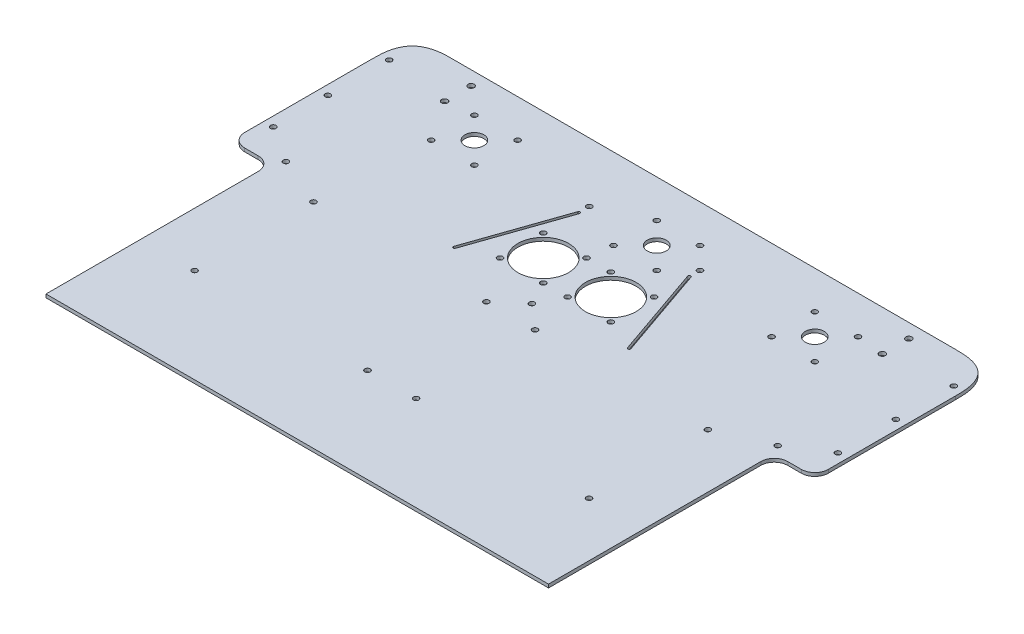
SolidWorks part; units mm, degrees
ref_plane "Front Plane" through (0, 0, 0) normal (0, 0, 1) x (1, 0, 0)
ref_plane "Top Plane" through (0, 0, 0) normal (0, 1, 0) x (1, 0, 0)
ref_plane "Right Plane" through (0, 0, 0) normal (1, 0, 0) x (0, 0, -1)
sketch "Sketch1" plane through (0, 0, 0) normal (0, 1, 0) x (1, 0, 0)
  line L1 (-103.134, 171.9149) -> (328.866, 171.9149)
  line L2 (-103.134, 171.9149) -> (-103.134, -28.0851)
  line L3 (-103.134, -28.0851) -> (328.866, -28.0851)
  line L4 (328.866, 171.9149) -> (328.866, -28.0851)
extrude "Boss-Extrude1" add sketch "Sketch1" along normal blind 2.5 contours L1 L4 L3 L2
sketch "Sketch3" plane through (0, 2.5, 0) normal (0, 1, 0) x (1, 0, 0)
  line L0 (-13.134, 71.9149) -> (-29.1359, 55.9131)
  line L1 (2.8678, 87.9167) -> (-29.1359, 87.9167)
  line L2 (2.8678, 87.9167) -> (2.8678, 55.9131)
  line L3 (2.8678, 55.9131) -> (-29.1359, 55.9131)
  line L4 (-29.1359, 87.9167) -> (-29.1359, 55.9131)
  line L5 (2.8678, 87.9167) -> (-29.1359, 55.9131) construction
  line L6 (2.8678, 55.9131) -> (-29.1359, 87.9167) construction
  line L7 (-103.134, 71.9149) -> (-13.134, 71.9149)
  line L8 (-103.134, 171.9149) -> (-103.134, -28.0851) construction
  line L9 (238.866, 71.9149) -> (238.866, 115.9149)
  line L14 (62.253, -0.3819) -> (46.2512, -16.3837)
  line L15 (238.866, 115.9149) -> (328.866, 115.9149)
  line L18 (328.866, 171.9149) -> (328.866, -28.0851) construction
  line L19 (238.866, 71.9149) -> (222.8641, 55.9131)
  line L20 (254.8678, 87.9167) -> (222.8641, 87.9167)
  line L21 (254.8678, 87.9167) -> (254.8678, 55.9131)
  line L22 (254.8678, 55.9131) -> (222.8641, 55.9131)
  line L23 (222.8641, 87.9167) -> (222.8641, 55.9131)
  line L24 (254.8678, 87.9167) -> (222.8641, 55.9131) construction
  line L25 (254.8678, 55.9131) -> (222.8641, 87.9167) construction
  line L27 (328.866, 71.9149) -> (238.866, 71.9149)
  line L28 (238.866, 115.9149) -> (238.866, 171.9149)
  line L29 (238.866, 171.9149) -> (328.866, 171.9149)
  line L30 (328.866, 115.9149) -> (328.866, 171.9149)
  line L31 (328.866, 115.9149) -> (-169.3435, 115.9149)
  line L32 (328.866, 115.9149) -> (328.866, 173.2785)
  line L33 (328.866, 173.2785) -> (-169.3435, 173.2785)
  line L34 (-169.3435, 115.9149) -> (-169.3435, 173.2785)
  line L35 (78.2549, 15.6199) -> (46.2512, 15.6199)
  line L36 (78.2549, 15.6199) -> (78.2549, -16.3837)
  line L37 (78.2549, -16.3837) -> (46.2512, -16.3837)
  line L38 (46.2512, 15.6199) -> (46.2512, -16.3837)
  line L39 (78.2549, 15.6199) -> (46.2512, -16.3837) construction
  line L40 (78.2549, -16.3837) -> (46.2512, 15.6199) construction
  circle A0 centre (-13.134, 71.9149) radius 7
  circle A1 centre (-29.1359, 55.9131) radius 2
  circle A2 centre (-29.1359, 87.9167) radius 2
  circle A3 centre (2.8678, 87.9167) radius 2
  circle A4 centre (2.8678, 55.9131) radius 2
  circle A10 centre (238.866, 71.9149) radius 7
  circle A11 centre (222.8641, 55.9131) radius 2
  circle A12 centre (222.8641, 87.9167) radius 2
  circle A13 centre (254.8678, 87.9167) radius 2
  circle A14 centre (254.8678, 55.9131) radius 2
  circle A15 centre (62.253, -0.3819) radius 7
  circle A16 centre (46.2512, -16.3837) radius 2
  circle A17 centre (46.2512, 15.6199) radius 2
  circle A18 centre (78.2549, 15.6199) radius 2
  circle A19 centre (78.2549, -16.3837) radius 2
  point P10 (328.866, 71.9149)
extrude "Cut-Extrude1" cut sketch "Sketch3" against normal blind 2.5 contours A2 | A3 | A4 | A1 | A0 | A11 | A14 | A13 | A10 | A12 | L32 L31 L34 L33
sketch "Sketch5" plane through (0, 2.5, 0) normal (0, 1, 0) x (1, 0, 0)
  line L0 (263.7413, -28.0851) -> (263.7413, -18.0851)
  line L3 (-103.134, -28.0851) -> (328.866, -28.0851) construction
  line L5 (263.7413, -18.0851) -> (328.866, -18.0851)
  line L6 (263.7413, -18.0851) -> (263.7413, -28.0851)
  line L7 (263.7413, -28.0851) -> (328.866, -28.0851)
  line L8 (328.866, -18.0851) -> (328.866, -28.0851)
  line L9 (263.7413, -18.0851) -> (-103.134, -18.0851)
  line L10 (263.7413, -18.0851) -> (263.7413, -28.0851)
  line L11 (263.7413, -28.0851) -> (-103.134, -28.0851)
  line L12 (-103.134, -18.0851) -> (-103.134, -28.0851)
  line M12 (328.866, -28.0851) -> (328.866, 115.9149)
  line M14 (-103.134, 115.9149) -> (-103.134, -28.0851)
  line M15 (-103.134, -28.0851) -> (328.866, -28.0851)
extrude "Cut-Extrude3" cut sketch "Sketch5" against normal blind 2.5 contours L0 L9 M14 M15 | L5 L0 M15 M12 region at (80.3036, 2.5, 23.0851) region at (296.3036, 2.5, 23.0851)
sketch "Sketch6" plane through (0, 2.5, 0) normal (0, 1, 0) x (1, 0, 0)
  line L0 (328.866, -18.0851) -> (-103.134, -18.0851) construction
  line L1 (112.866, -18.0851) -> (112.866, 21.9149)
  line L2 (112.866, 21.9149) -> (137.866, 21.9149)
  line L3 (112.866, 21.9149) -> (87.866, 21.9149)
  line L4 (87.866, 21.9149) -> (71.8641, 5.9131)
  line L5 (103.8678, 37.9167) -> (71.8641, 37.9167)
  line L6 (103.8678, 37.9167) -> (103.8678, 5.9131)
  line L7 (103.8678, 5.9131) -> (71.8641, 5.9131)
  line L8 (71.8641, 37.9167) -> (71.8641, 5.9131)
  line L9 (103.8678, 37.9167) -> (71.8641, 5.9131) construction
  line L10 (103.8678, 5.9131) -> (71.8641, 37.9167) construction
  line L11 (137.866, 21.9149) -> (121.8641, 5.9131)
  line L12 (153.8678, 37.9167) -> (121.8641, 37.9167)
  line L13 (153.8678, 37.9167) -> (153.8678, 5.9131)
  line L14 (153.8678, 5.9131) -> (121.8641, 5.9131)
  line L15 (121.8641, 37.9167) -> (121.8641, 5.9131)
  line L16 (153.8678, 37.9167) -> (121.8641, 5.9131) construction
  line L17 (153.8678, 5.9131) -> (121.8641, 37.9167) construction
  circle A0 centre (137.866, 21.9149) radius 18.75
  circle A1 centre (87.866, 21.9149) radius 18.75
  circle A2 centre (87.866, 21.9149) radius 7
  circle A3 centre (71.8641, 5.9131) radius 2
  circle A4 centre (71.8641, 37.9167) radius 2
  circle A5 centre (103.8678, 37.9167) radius 2
  circle A6 centre (103.8678, 5.9131) radius 2
  circle A7 centre (137.866, 21.9149) radius 7
  circle A8 centre (121.8641, 5.9131) radius 2
  circle A9 centre (121.8641, 37.9167) radius 2
  circle A10 centre (153.8678, 37.9167) radius 2
  circle A11 centre (153.8678, 5.9131) radius 2
  point P0 (112.866, -18.0851)
extrude "Cut-Extrude4" cut sketch "Sketch6" against normal blind 2.5 contours A11 | A8 | A10 | A9 | A5 | A6 | A3 | A4
sketch "Sketch8" plane through (0, 2.5, 0) normal (0, 1, 0) x (1, 0, 0)
  line L2 (153.8678, 5.9131) -> (153.8678, 90.0973)
  line L3 (153.8678, 90.0973) -> (71.8641, 90.0973)
  line L4 (71.8641, 90.0973) -> (71.8641, 5.9131)
  line L5 (153.8678, 64.0929) -> (71.8641, 64.0929)
  line L10 (177.527, -4.0851) -> (153.8678, 64.0929) construction
  line L14 (176.5823, -4.4129) -> (152.9231, 63.7651)
  line L15 (178.4718, -3.7572) -> (154.8125, 64.4208)
  line L16 (48.2049, -4.0851) -> (71.8641, 64.0929) construction
  line L17 (47.2602, -3.7572) -> (70.9194, 64.4208)
  line L18 (49.1496, -4.4129) -> (72.8089, 63.7651)
  arc A6 (176.5823, -4.4129) -> (178.4718, -3.7572) centre (177.527, -4.0851) ccw
  arc A7 (154.8125, 64.4208) -> (152.9231, 63.7651) centre (153.8678, 64.0929) ccw
  arc A8 (47.2602, -3.7572) -> (49.1496, -4.4129) centre (48.2049, -4.0851) ccw
  arc A9 (72.8089, 63.7651) -> (70.9194, 64.4208) centre (71.8641, 64.0929) ccw
  point P17 (177.527, 5.9131)
  point P18 (48.2049, 5.9131)
  point P19 (165.6974, 30.0039)
  point P22 (112.866, -4.0851)
  point P27 (60.0345, 30.0039)
extrude "Cut-Extrude5" cut sketch "Sketch8" against normal blind 2.5 contours L17 A9 L18 A8 | L15 A7 L14 A6
fillet "Fillet1" radius 30 2 edges at (-103.134, 1.25, -115.9149) (328.866, 1.25, -115.9149) curvature continuous yes
sketch "Sketch9" plane through (0, 2.5, 0) normal (0, 1, 0) x (1, 0, 0)
  line L0 (328.866, 62.6221) -> (321.866, 62.6221)
  line L1 (328.866, 85.9149) -> (328.866, -18.0851) construction
  line L2 (321.866, 109.7214) -> (321.866, -11.8915)
  line L3 (321.866, 6.0103) -> (321.866, -11.8915)
  line L4 (321.866, 109.7214) -> (321.866, 91.8196)
  line L5 (321.866, 91.8196) -> (321.866, 109.7214)
  line L6 (-103.134, 46.4673) -> (-96.134, 46.4673)
  line L7 (-103.134, 85.9149) -> (-103.134, -18.0851) construction
  line L8 (-96.134, 46.4673) -> (-96.134, 109.7214)
  line L9 (-96.134, 109.7214) -> (-96.134, -11.8916)
  line L10 (-96.134, -11.8916) -> (-96.134, 6.0103)
  line L11 (-96.134, 109.7214) -> (-96.134, 97.3154)
  line L12 (-96.134, 109.7214) -> (-96.134, 91.8196)
  circle A0 centre (321.866, 6.0103) radius 2
  circle A1 centre (321.866, 48.9149) radius 2
  circle A2 centre (321.866, 91.8196) radius 2
  circle A3 centre (-96.134, 46.4673) radius 2
  circle A4 centre (-96.134, 91.8196) radius 2
  circle A5 centre (-96.134, 6.0103) radius 2
  spline S0 degree 2 poles (328.866, 85.9149) (328.866, 87.9765) (328.8467, 89.0459) (328.8162, 90.7467) (328.7231, 92.1742) (328.5043, 95.5283) (327.8783, 98.3317) (326.3274, 105.2776) (322.2688, 109.3319) (318.2198, 113.3765) (311.2895, 114.9258) (308.4764, 115.5546) (305.1048, 115.7733) (303.6844, 115.8655) (301.9893, 115.8958) (300.9233, 115.9149) (298.866, 115.9149) knots 0 0 0 0.0625 0.0625 0.125 0.125 0.25 0.25 0.5 0.5 0.75 0.75 0.875 0.875 0.9375 0.9375 1 1 1 construction
  spline S1 degree 2 poles (298.866, -18.0851) (300.9275, -18.0851) (301.997, -18.0659) (303.6978, -18.0353) (305.1253, -17.9422) (308.4794, -17.7234) (311.2827, -17.0975) (318.2287, -15.5466) (322.283, -11.4879) (326.3276, -7.4389) (327.8768, -0.5086) (328.5057, 2.3045) (328.7244, 5.6761) (328.8165, 7.0965) (328.8469, 8.7916) (328.866, 9.8575) (328.866, 11.9149) knots 0 0 0 0.0625 0.0625 0.125 0.125 0.25 0.25 0.5 0.5 0.75 0.75 0.875 0.875 0.9375 0.9375 1 1 1 construction
  spline S2 degree 2 poles (-73.134, 115.9149) (-75.1956, 115.9149) (-76.2651, 115.8957) (-77.9658, 115.8651) (-79.3933, 115.772) (-82.7474, 115.5532) (-85.5508, 114.9273) (-92.4967, 113.3764) (-96.551, 109.3177) (-100.5957, 105.2687) (-102.1449, 98.3384) (-102.7737, 95.5254) (-102.9924, 92.1538) (-103.0846, 90.7333) (-103.1149, 89.0383) (-103.134, 87.9723) (-103.134, 85.9149) knots 0 0 0 0.0625 0.0625 0.125 0.125 0.25 0.25 0.5 0.5 0.75 0.75 0.875 0.875 0.9375 0.9375 1 1 1 construction
  spline S3 degree 2 poles (-103.134, 11.9149) (-103.134, 9.8534) (-103.1148, 8.7839) (-103.0842, 7.0831) (-102.9911, 5.6556) (-102.7723, 2.3015) (-102.1464, -0.5019) (-100.5955, -7.4478) (-96.5368, -11.5021) (-92.4879, -15.5467) (-85.5575, -17.0959) (-82.7445, -17.7248) (-79.3729, -17.9435) (-77.9525, -18.0356) (-76.2574, -18.066) (-75.1914, -18.0851) (-73.134, -18.0851) knots 0 0 0 0.0625 0.0625 0.125 0.125 0.25 0.25 0.5 0.5 0.75 0.75 0.875 0.875 0.9375 0.9375 1 1 1 construction
extrude "Cut-Extrude6" cut sketch "Sketch9" against normal blind 2.5 contours A0 | A1 | A2 | A5 | A3 | A4
sketch "Sketch10" plane through (0, 2.5, 0) normal (0, 1, 0) x (1, 0, 0)
  line L0 (232.1904, -18.0851) -> (232.1904, -11.5851)
  line L1 (328.866, -18.0851) -> (-103.134, -18.0851) construction
  line L2 (322.1851, -11.5851) -> (-96.4532, -11.5851)
  line L3 (322.1851, -11.5851) -> (232.1904, -11.5851)
  line L4 (322.1851, -11.5851) -> (232.1904, -11.5851)
  line L5 (322.1851, -11.5851) -> (232.1904, -11.5851)
  line L6 (322.1851, -11.5851) -> (294.9418, -11.5851)
  line L7 (-96.4532, -11.5851) -> (-78.7572, -11.5851)
  line L8 (-96.4532, -11.5851) -> (-69.2097, -11.5851)
  circle A0 centre (112.866, -11.5851) radius 2
  circle A3 centre (294.9418, -11.5851) radius 2
  circle A4 centre (-69.2097, -11.5851) radius 2
  spline S0 degree 2 poles (298.866, -18.0851) (300.9275, -18.0851) (301.997, -18.0659) (303.6978, -18.0353) (305.1253, -17.9422) (308.4794, -17.7234) (311.2827, -17.0975) (318.2287, -15.5466) (322.283, -11.4879) (326.3276, -7.4389) (327.8768, -0.5086) (328.5057, 2.3045) (328.7244, 5.6761) (328.8165, 7.0965) (328.8469, 8.7916) (328.866, 9.8575) (328.866, 11.9149) knots 0 0 0 0.0625 0.0625 0.125 0.125 0.25 0.25 0.5 0.5 0.75 0.75 0.875 0.875 0.9375 0.9375 1 1 1 construction
  spline S1 degree 2 poles (-103.134, 11.9149) (-103.134, 9.8534) (-103.1148, 8.7839) (-103.0842, 7.0831) (-102.9911, 5.6556) (-102.7723, 2.3015) (-102.1464, -0.5019) (-100.5955, -7.4478) (-96.5368, -11.5021) (-92.4879, -15.5467) (-85.5575, -17.0959) (-82.7445, -17.7248) (-79.3729, -17.9435) (-77.9525, -18.0356) (-76.2574, -18.066) (-75.1914, -18.0851) (-73.134, -18.0851) knots 0 0 0 0.0625 0.0625 0.125 0.125 0.25 0.25 0.5 0.5 0.75 0.75 0.875 0.875 0.9375 0.9375 1 1 1 construction
extrude "Cut-Extrude7" cut sketch "Sketch10" against normal blind 2.5 contours A4 | A0 | A3
extrude "Cut-Extrude8" cut sketch "Sketch6<3>" against normal blind 10 contours A1 | A0
sketch "Sketch6<3>" plane through (0, 2.5, 0) normal (0, 1, 0) x (1, 0, 0) same geometry as "Sketch6"
sketch "Sketch12" plane through (0, 2.5, 0) normal (0, 1, 0) x (1, 0, 0)
  line L0 (121.8641, 37.9167) -> (121.8641, 71.9149)
  line L1 (238.866, 71.9149) -> (-13.134, 71.9149)
  line L3 (121.8641, 71.9149) -> (105.8623, 55.9131)
  line L4 (137.866, 87.9167) -> (105.8623, 87.9167)
  line L5 (137.866, 87.9167) -> (137.866, 55.9131)
  line L6 (137.866, 55.9131) -> (105.8623, 55.9131)
  line L7 (105.8623, 87.9167) -> (105.8623, 55.9131)
  line L8 (137.866, 87.9167) -> (105.8623, 55.9131) construction
  line L9 (137.866, 55.9131) -> (105.8623, 87.9167) construction
  circle A1 centre (121.8641, 71.9149) radius 7
  circle A2 centre (105.8623, 55.9131) radius 2
  circle A3 centre (105.8623, 87.9167) radius 2
  circle A4 centre (137.866, 87.9167) radius 2
  circle A5 centre (137.866, 55.9131) radius 2
extrude "Cut-Extrude9" cut sketch "Sketch12" against normal blind 10 contours A5 | A4 | A3 | A2 | A1
sketch "Sketch13" plane through (0, 2.5, 0) normal (0, 1, 0) x (1, 0, 0)
  line L0 (328.866, 85.9149) -> (274.866, 85.9149)
  line L1 (274.866, 85.9149) -> (274.866, 105.5149)
  line L2 (-103.134, 85.9149) -> (-49.134, 85.9149)
  line L3 (-49.134, 85.9149) -> (-49.134, 105.5149)
  circle A0 centre (274.866, 85.9149) radius 2.25
  circle A1 centre (274.866, 105.5149) radius 2.25
  circle A2 centre (-49.134, 85.9149) radius 2.25
  circle A3 centre (-49.134, 105.5149) radius 2.25
extrude "Cut-Extrude10" cut sketch "Sketch13" against normal blind 10 contours A0 | A1 | A2 | A3
sketch "Sketch14" plane through (0, 2.5, 0) normal (0, 1, 0) x (1, 0, 0)
  line L0 (153.8678, 37.9167) -> (121.8641, 71.9149)
  line L1 (121.8641, 71.9149) -> (153.8678, 71.9149)
  line L2 (71.8641, 37.9167) -> (71.8641, 71.9149)
  circle A0 centre (153.8678, 71.9149) radius 2
  circle A1 centre (71.8641, 71.9149) radius 2
extrude "Cut-Extrude12" cut sketch "Sketch14" against normal blind 2.5 contours A0 | A1
sketch "Sketch19" plane through (0, 2.5, 0) normal (0, 1, 0) x (1, 0, 0)
  line L0 (-73.134, -18.0851) -> (298.866, -18.0851)
  line L1 (-73.134, -18.0851) -> (-73.134, -185.2034)
  line L2 (298.866, -18.0851) -> (298.866, -185.2034)
  line L3 (-73.134, -185.2034) -> (298.866, -185.2034)
extrude "Boss-Extrude5" add sketch "Sketch19" against normal blind 2.5
fillet "Fillet3" radius 10 4 edges at (-103.134, 1.25, 18.0851) (-73.134, 1.25, 18.0851) (328.866, 1.25, 18.0851) (298.866, 1.25, 18.0851)
sketch "Sketch21" plane through (0, 2.5, 0) normal (0, 1, 0) x (1, 0, 0)
  line L1 (298.866, -185.2034) -> (258.866, -185.2034)
  line L2 (298.866, -185.2034) -> (298.866, -115.2034)
  line L3 (298.866, -115.2034) -> (258.866, -115.2034)
  line L4 (258.866, -185.2034) -> (258.866, -115.2034)
  line L5 (258.866, -115.2034) -> (130.866, -115.2034)
  line L6 (258.866, -115.2034) -> (258.866, -27.2034)
  line L7 (258.866, -27.2034) -> (130.866, -27.2034)
  line L8 (130.866, -115.2034) -> (130.866, -27.2034)
  line L9 (-73.134, -185.2034) -> (-33.134, -185.2034)
  line L10 (-73.134, -185.2034) -> (-73.134, -115.2034)
  line L11 (-73.134, -115.2034) -> (-33.134, -115.2034)
  line L12 (-33.134, -185.2034) -> (-33.134, -115.2034)
  line L13 (-33.134, -115.2034) -> (94.866, -115.2034)
  line L14 (-33.134, -115.2034) -> (-33.134, -27.2034)
  line L15 (-33.134, -27.2034) -> (94.866, -27.2034)
  line L16 (94.866, -115.2034) -> (94.866, -27.2034)
  circle A0 centre (258.866, -115.2034) radius 2
  circle A1 centre (130.866, -115.2034) radius 2
  circle A2 centre (94.866, -115.2034) radius 2
  circle A3 centre (-33.134, -115.2034) radius 2
  circle A4 centre (-33.134, -27.2034) radius 2
  circle A5 centre (94.866, -27.2034) radius 2
  circle A6 centre (258.866, -27.2034) radius 2
  circle A7 centre (130.866, -27.2034) radius 2
extrude "Cut-Extrude14" cut sketch "Sketch21" against normal blind 2.5 contours A0 | A6 | A7 | A5 | A1 | A2 | A4 | A3
